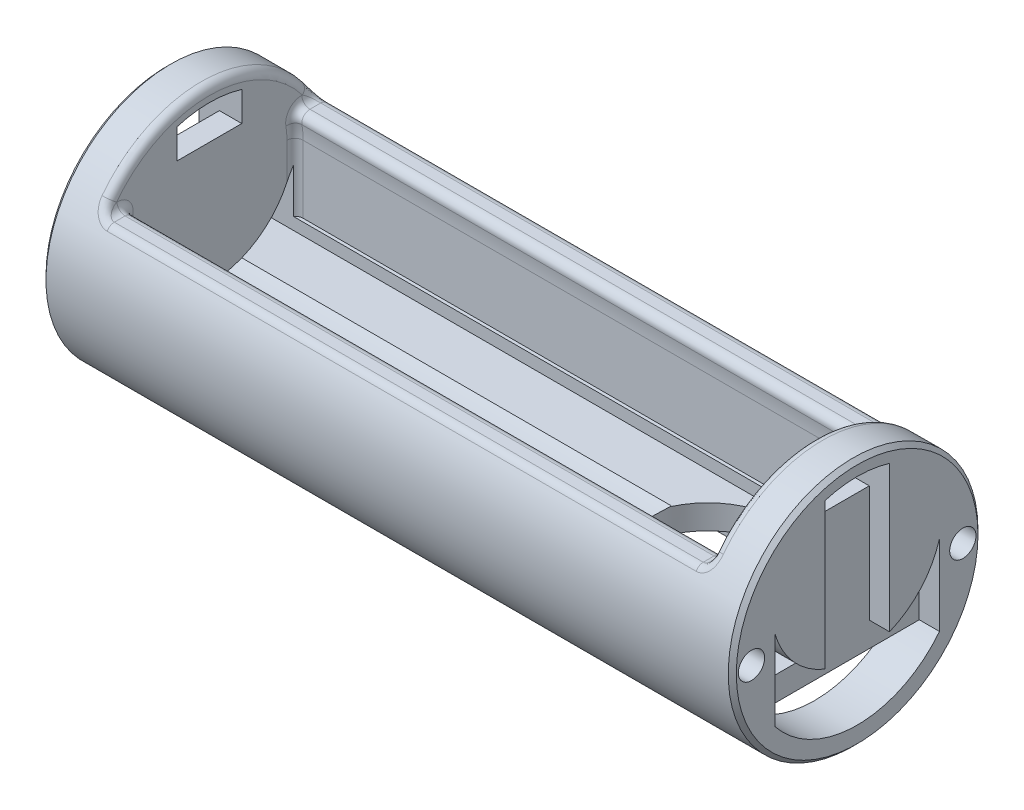
SolidWorks part; units mm, degrees
material "Nylon 101"
ref_plane "Front Plane" through (0, 0, 0) normal (0, 0, 1) x (1, 0, 0)
ref_plane "Top Plane" through (0, 0, 0) normal (0, 1, 0) x (1, 0, 0)
ref_plane "Right Plane" through (0, 0, 0) normal (1, 0, 0) x (0, 0, -1)
sketch "Sketch1" plane through (0, 0, 0) normal (1, 0, 0) x (0, 0, -1)
  circle A0 centre (0, 0) radius 15.6845
  dimension "D1" = 31.369
extrude "Boss-Extrude1" add sketch "Sketch1" along normal blind 86.7 contours A0
ref_plane "Plane1" through (43.35, 0, 0) normal (1, 0, 0) x (0, 0, -1)
sketch "Sketch2" plane through (43.35, 0, 0) normal (1, 0, 0) x (0, 0, -1)
  line L0 (-13.4193, -8.1195) -> (13.4193, -8.1195)
  line L1 (-13.561, 7.8805) -> (13.561, 7.8805)
  line L2 (-10.668, -11.4977) -> (-10.668, -8.1195)
  line L3 (10.668, -11.4977) -> (10.668, -8.1195)
  line L4 (-10.75, 4.9345) -> (-10.75, -3.5495)
  line L5 (-10.75, -3.5495) -> (10.75, -3.5495)
  line L6 (10.75, -3.5495) -> (10.75, 4.9345)
  line L7 (-10.668, -11.4977) -> (10.668, -11.4977) construction
  circle A0 centre (0, 4.9345) radius 10.75
  circle A2 centre (0, 0) radius 15.6845
  circle A3 centre (0, 0) radius 15.6845 construction
  circle A4 centre (0, 0) radius 15.6845
  point P9 (0, -15.6845)
  dimension "D1" = 21.5
  dimension "D2" = 16
  dimension "D3" = 3.3782
  dimension "D4" = 21.336
  dimension "D6" = 11.43
  dimension "D5" = 0
extrude "Cut-Extrude3" cut sketch "Sketch2" against normal mid plane 76 contours L7 A4 | L2 L7 L3 L0 | A0 L4 L5 | A0 L1 L5 | L5 A0 | A0 L5 L6 | L1 A4 A0 | L1 A0 | A0 A4 L1 region at (43.35, -9.8086, 0) region at (43.35, 10.9052, 9.6739) region at (43.35, -13.1932, 0) region at (43.35, 11.1256, 0) region at (43.35, 2.4984, 0) region at (43.35, 10.9052, -9.6739) region at (43.35, -1.519, 9.5612) region at (43.35, -1.519, -9.5612) region at (43.35, -4.4646, 0)
fillet "Fillet1" radius 1.016 22 edges at (5.35, 0.6925, -10.75) (81.35, 0.6925, -10.75) (81.35, 0.6925, 10.75) (5.35, 0.6925, 10.75) (5.35, 6.4218, -10.6466) (81.35, 6.4218, -10.6466) (81.35, 15.6845, 0) (81.35, 6.4218, 10.6466) (5.35, 15.6845, 0) (5.35, 6.4218, 10.6466) (5.35, 7.8805, -11.9497) (81.35, 7.8805, -11.9497) (81.35, 7.8805, 11.9497) (5.35, 7.8805, 11.9497) (5.35, -9.8086, 10.668) (81.35, -9.8086, 10.668) (81.35, -9.8086, -10.668) (5.35, -9.8086, -10.668) (43.35, 7.8805, -10.3385) (43.35, 7.8805, -13.561) (43.35, 7.8805, 13.561) (43.35, 7.8805, 10.3385)
sketch "Sketch3" plane through (0, 0, 0) normal (-1, 0, 0) x (0, 0, 1)
  line L0 (-4.064, 9.5885) -> (4.064, 9.5885)
  line L4 (-9.652, -8.1195) -> (9.652, -8.1195) construction
  line L9 (-10.3369, -8.1195) -> (10.3369, -8.1195)
  line L10 (-15.6845, 0) -> (15.6845, 0)
  line L11 (-4.064, -8.1195) -> (4.064, -8.1195)
  line L12 (-4.064, -8.1195) -> (-4.064, 13.2994)
  line L14 (4.064, -8.1195) -> (4.064, 13.2994)
  line L15 (-10.3369, -8.1195) -> (-10.3369, 1.9831)
  line L16 (10.3369, -8.1195) -> (10.3369, 1.9831)
  line L17 (-10.3369, -5.0715) -> (10.3369, -5.0715)
  line L26 (-10.3369, -8.1195) -> (10.3369, -8.1195)
  arc A0 (-13.8823, -0.8208) -> (-13.819, -1.5576) centre (0, 0) ccw
  circle A1 centre (0, 0) radius 15.6845
  circle A4 centre (0, 0) radius 13.9065 construction
  arc A8 (-8.8927, -9.6798) -> (-7.1667, -11.0189) centre (0, 0) ccw
  arc A9 (-7.1667, -11.0189) -> (8.0889, -10.3608) centre (0, 0) ccw
  arc A10 (8.0889, -10.3608) -> (8.9404, -9.6357) centre (0, 0) ccw
  arc A11 (-8.8927, -9.6798) -> (-10.3369, -8.1195) centre (0, 0) cw
  arc A12 (8.9404, -9.6357) -> (10.3369, -8.1195) centre (0, 0) ccw
  arc A14 (4.064, 13.2994) -> (-4.064, 13.2994) centre (0, 0) ccw
  arc A15 (-6.6018, -3.5495) -> (6.6018, -3.5495) centre (0, 4.9345) ccw construction
  arc A16 (-6.6018, -3.5495) -> (6.6018, -3.5495) centre (0, 4.9345) ccw
  arc A17 (-10.3369, 1.9831) -> (10.3369, 1.9831) centre (0, 4.9345) ccw
  circle A18 centre (-13.2715, 0) radius 1.651
  circle A19 centre (13.2715, 0) radius 1.651
  circle A20 centre (0, 0) radius 15.6845 construction
  circle A21 centre (0, 0) radius 15.6845
  arc A22 (9.652, -12.3629) -> (10.668, -11.4977) centre (0, 0) ccw construction
  arc A23 (-10.668, -11.4977) -> (-9.652, -12.3629) centre (0, 0) ccw construction
  arc A24 (-9.652, -12.3629) -> (9.652, -12.3629) centre (0, 0) ccw construction
  arc A25 (9.652, -12.3629) -> (10.668, -11.4977) centre (0, 0) ccw
  arc A26 (-10.668, -11.4977) -> (-9.652, -12.3629) centre (0, 0) ccw
  arc A27 (-9.652, -12.3629) -> (9.652, -12.3629) centre (0, 0) ccw
  point P8 (0, 13.9065)
  point P13 (0, -5.0715)
  dimension "D4" = 3.302
  dimension "D5" = 2.54
  dimension "D9" = 1.778
  dimension "D2" = 8.128
  dimension "D3" = 3.048
  dimension "D6" = 2.413
  dimension "D7" = 2.413
  dimension "D10" = 4.318
  dimension "D1" = 0
  dimension "D8" = 1.778
extrude "Cut-Extrude4" cut sketch "Sketch3" against normal through all and the other way through all contours A17 L10 L15 L17 L12 A16 | A17 A16 L14 L17 L16 L10 | A17 L10 L16 | A17 L15 L10 | L10 A18 | L10 A18 | A10 A12 L9 A11 A8 A9 | L10 A19 | L10 A19 | L14 A14 L12 L0 region at (0, 11.6512, 0) region at (0, -3.3038, -8.4695) region at (0, 0.6264, -10.0867) region at (0, 0.6264, 10.0867) region at (0, -3.3038, 8.4695) region at (0, -0.7007, -13.2715) region at (0, 0.7007, -13.2715) region at (0, -10.1666, 0) region at (0, 0.7007, 13.2715) region at (0, -0.7007, 13.2715)
extrude "Cut-Extrude5" cut sketch "Sketch3<3>" against normal blind 2.54 contours L17 L15 L9 L12 | L17 L12 L9 L14 | L17 L14 L9 L16 | L12 A16 L14 L10 | A16 L12 L17 L14 | L14 A14 L12 L10 | L17 A16 | L11 L14 A14 L12 region at (0, 4.7943, 0) region at (0, -2.5353, 0) region at (0, -6.8263, 0) region at (0, -6.5955, -7.2004) region at (0, -5.37, 0) region at (0, -6.5955, 7.2004)
sketch "Sketch3<3>" plane through (0, 0, 0) normal (-1, 0, 0) x (0, 0, 1) same geometry as "Sketch3"
mirror "Mirror3" about plane through (43.35, 0, 0) normal (1, 0, 0) of "Cut-Extrude5"
sketch "Sketch4" plane through (0, -8.1195, 0) normal (0, -1, 0) x (1, 0, 0)
  line L8 (81.0844, -10.3369) -> (84.16, -10.3369)
  line L9 (84.16, -10.3369) -> (84.16, 10.3369)
  line L10 (84.16, 10.3369) -> (81.0844, 10.3369)
  line L11 (80.334, 10.668) -> (6.366, 10.668)
  line L12 (5.6156, 10.3369) -> (2.54, 10.3369)
  line L13 (2.54, 10.3369) -> (2.54, -10.3369)
  line L14 (2.54, -10.3369) -> (5.6156, -10.3369)
  line L15 (6.366, -10.668) -> (80.334, -10.668)
  line L16 (81.0844, -10.3369) -> (84.16, -10.3369)
  line L17 (84.16, -10.3369) -> (84.16, 10.3369)
  line L18 (84.16, 10.3369) -> (81.0844, 10.3369)
  line L19 (80.334, 10.668) -> (6.366, 10.668)
  line L20 (5.6156, 10.3369) -> (2.54, 10.3369)
  line L21 (2.54, 10.3369) -> (2.54, -10.3369)
  line L22 (2.54, -10.3369) -> (5.6156, -10.3369)
  line L23 (6.366, -10.668) -> (80.334, -10.668)
  circle A0 centre (67.9338, 0) radius 9.525
  arc A4 (81.0844, 10.3369) -> (80.334, 10.668) centre (80.334, 9.652) ccw
  arc A5 (6.366, 10.668) -> (5.6156, 10.3369) centre (6.366, 9.652) ccw
  arc A6 (5.6156, -10.3369) -> (6.366, -10.668) centre (6.366, -9.652) ccw
  arc A7 (80.334, -10.668) -> (81.0844, -10.3369) centre (80.334, -9.652) ccw
  arc A8 (81.0844, 10.3369) -> (80.334, 10.668) centre (80.334, 9.652) ccw
  arc A9 (6.366, 10.668) -> (5.6156, 10.3369) centre (6.366, 9.652) ccw
  arc A10 (5.6156, -10.3369) -> (6.366, -10.668) centre (6.366, -9.652) ccw
  arc A11 (80.334, -10.668) -> (81.0844, -10.3369) centre (80.334, -9.652) ccw
  dimension "D1" = 0
extrude "Cut-Extrude6" cut sketch "Sketch4" against normal through all contours A0 region at (67.9338, -8.1195, 0)
chamfer "Chamfer1" distance 0.508 angle 45 2 edges at (86.7, 0, -15.6845) (0, 0, -15.6845)
